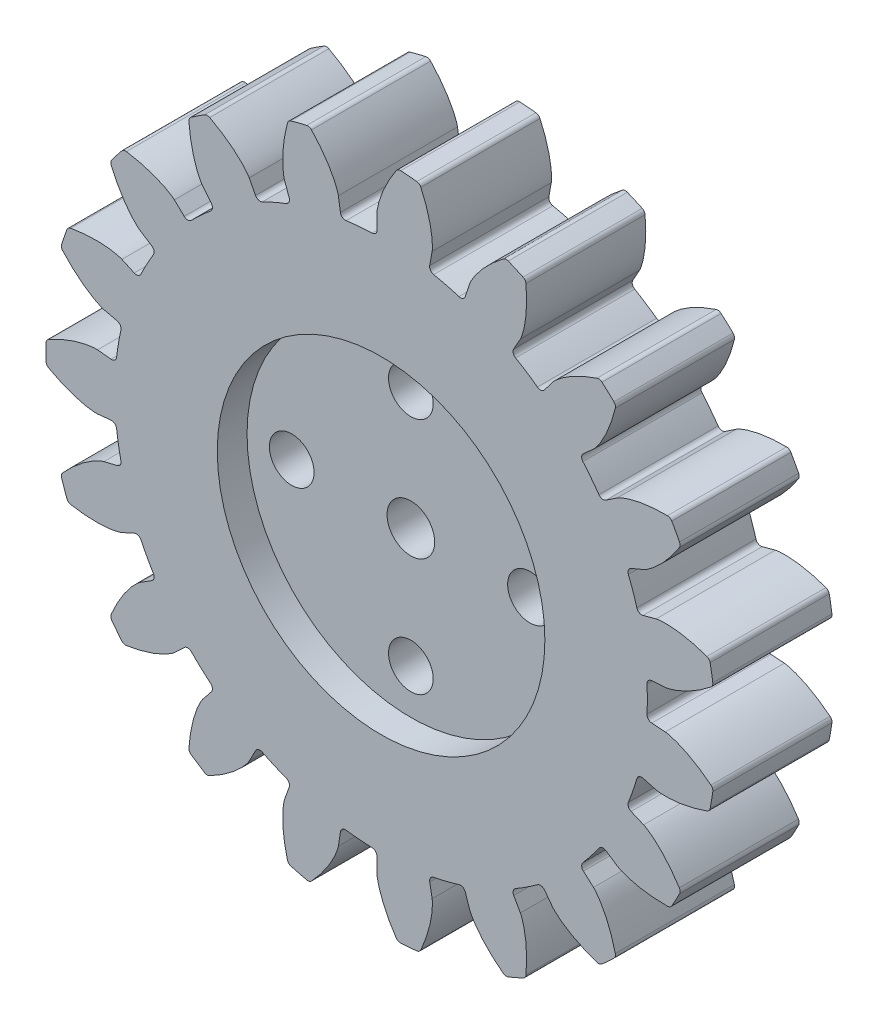
SolidWorks part; units mm, degrees
ref_plane "Front Plane" through (0, 0, 0) normal (0, 0, 1) x (1, 0, 0)
ref_plane "Top Plane" through (0, 0, 0) normal (0, 1, 0) x (1, 0, 0)
ref_plane "Right Plane" through (0, 0, 0) normal (1, 0, 0) x (0, 0, -1)
sketch "Sketch10" plane through (0, 0, 0) normal (0, 0, 1) x (1, 0, 0)
  circle A0 centre (0, 0) radius 22.5
  circle A1 centre (0, 0) radius 1.25
  dimension "D1" = 2.5
  dimension "D2" = 45
extrude "Boss-Extrude5" add sketch "Sketch10" along normal blind 10
sketch "Sketch11" plane through (0, 0, 10) normal (0, 0, 1) x (1, 0, 0)
  line L0 (0, 0) -> (17.88, 0) construction
  line L3 (17.88, 0) -> (22.5005, 0)
  line L4 (0, 0) -> (17.839, 1.2108) construction
  line L5 (19.0859, 1.2954) -> (17.839, 1.2108)
  circle A0 centre (0, 0) radius 17.88 construction
  circle A1 centre (0, 0) radius 19.13 construction
  circle A2 centre (0, 0) radius 20.36 construction
  circle A11 centre (0, 0) radius 22.5005 construction
  arc A12 (22.5005, 0) -> (22.3031, 2.9739) centre (0, 0) ccw
  arc A13 (17.88, 0) -> (17.839, 1.2108) centre (0, 0) ccw
  spline S0 degree 4 poles (19.0859, 1.2954) (19.0913, 1.2959) (19.1065, 1.2973) (19.135, 1.3009) (19.1815, 1.308) (19.2405, 1.3189) (19.3165, 1.335) (19.4057, 1.3566) (19.5032, 1.3831) (19.6089, 1.415) (19.7138, 1.4494) (19.8179, 1.4861) (19.9212, 1.5249) (20.0458, 1.5745) (20.1943, 1.6376) (20.3667, 1.7165) (20.5606, 1.8121) (20.7565, 1.9161) (20.9477, 2.0237) (21.139, 2.1386) (21.3228, 2.254) (21.5117, 2.38) (21.685, 2.4995) (21.8768, 2.6401) (22.0309, 2.7556) (22.2316, 2.915) (22.3493, 3.0113) (22.4861, 3.1265) (22.5464, 3.1789) (22.5835, 3.2111) knots 0 0 0 0 0 0.005377 0.015084 0.028532 0.04661 0.064855 0.092111 0.119476 0.146842 0.174209 0.201575 0.228941 0.256307 0.307035 0.361767 0.4165 0.471232 0.525964 0.580697 0.635429 0.690161 0.744894 0.799626 0.854358 0.909091 0.954545 1 1 1 1 1 construction
  spline S1 degree 4 poles (19.0859, 1.2954) (19.0913, 1.2959) (19.1065, 1.2973) (19.135, 1.3009) (19.1815, 1.308) (19.2405, 1.3189) (19.3165, 1.335) (19.4057, 1.3566) (19.5032, 1.3831) (19.6089, 1.415) (19.7138, 1.4494) (19.8179, 1.4861) (19.9212, 1.5249) (20.0458, 1.5745) (20.1943, 1.6376) (20.3667, 1.7165) (20.5606, 1.8121) (20.7565, 1.9161) (20.9477, 2.0237) (21.139, 2.1386) (21.3228, 2.254) (21.5117, 2.38) (21.685, 2.4995) (21.8768, 2.6401) (22.0309, 2.7556) (22.1881, 2.8805) (22.2643, 2.9421) (22.3031, 2.9739) knots 0 0 0 0 0 0.005377 0.015084 0.028532 0.04661 0.064855 0.092111 0.119476 0.146842 0.174209 0.201575 0.228941 0.256307 0.307035 0.361767 0.4165 0.471232 0.525964 0.580697 0.635429 0.690161 0.744894 0.799626 0.854358 0.909091 0.909091 0.909091 0.909091 0.909091
  dimension "D1" = 40.72
  dimension "D2" = 38.26
  dimension "D3" = 35.76
extrude "Cut-Extrude1" cut sketch "Sketch11" against normal through all
mirror "Mirror1" about plane through (17.88, 0, 0) normal (0, -1, 0) of "Cut-Extrude1"
fillet "Fillet1" radius 0.34 4 edges at (17.839, -1.2108, 5) (22.3026, -2.9735, 5) (22.3026, 2.9735, 5) (17.839, 1.2108, 5)
pattern_circular "CirPattern1" count 19 over 360 about axis through (0, 0, 10) along (0, 0, -1) of "Cut-Extrude1", "Mirror1", "Fillet1" reverse direction yes
sketch "Sketch12" plane through (0, 0, 10) normal (0, 0, 1) x (1, 0, 0)
  circle A2 centre (0, 0) radius 11
  dimension "D1" = 22
extrude "Cut-Extrude2" cut sketch "Sketch12" against normal blind 2
sketch "Sketch13" plane through (0, 0, 8) normal (0, 0, 1) x (1, 0, 0)
  circle A0 centre (0, 0) radius 1.6
  dimension "D1" = 3.2
extrude "Cut-Extrude3" cut sketch "Sketch13" against normal through all
sketch "Sketch14" plane through (0, 0, 8) normal (0, 0, 1) x (1, 0, 0)
  line L0 (0, 0) -> (0, 11) construction
  line L1 (0, 0) -> (-11, 0) construction
  line L2 (0, 0) -> (0, -11) construction
  line L3 (0, 0) -> (11, 0) construction
  circle A0 centre (0, 0) radius 11 construction
  circle A1 centre (0, 0) radius 11 construction
  circle A2 centre (0, 8) radius 1.5
  circle A3 centre (8, 0) radius 1.5
  circle A4 centre (0, -8) radius 1.5
  circle A5 centre (-8, 0) radius 1.5
  dimension "D1" = 3
  dimension "D2" = 8
  dimension "D3" = 8
  dimension "D4" = 8
  dimension "D5" = 8
extrude "Cut-Extrude4" cut sketch "Sketch14" against normal blind 6
sketch "Croquis1" plane through (0, 0, 0) normal (0, 0, -1) x (-1, 0, 0)
  line L1 (-29.3017, 25.5972) -> (30.0749, 25.5972)
  line L2 (-29.3017, 25.5972) -> (-29.3017, -25.9289)
  line L3 (-29.3017, -25.9289) -> (30.0749, -25.9289)
  line L4 (30.0749, 25.5972) -> (30.0749, -25.9289)
extrude "Cortar-Extruir1" cut sketch "Croquis1" against normal blind 2
equation "\"P\"= 0.466657"
equation "\"z\"= 19"
equation "\"α\"= 20"
equation "\"s\"= 5"
equation "\"D_b\"= 2.5"
equation "\"c\"= 0.157 / \"P\""
equation "\"D_p\"= \"z\" / \"P\""
equation "\"D_base\"= \"D_p\" * cos ( \"α\" )"
equation "\"h_a\"= 1 / \"P\""
equation "\"h_d\"= 1 / \"P\" + \"c\""
equation "\"P_c\"= pi / \"P\""
equation "\"D_a\"= \"D_p\" + ( 2 * \"h_a\" )"
equation "\"D_d\"= \"D_p\" - ( 2 * \"h_d\" )"
equation "\"φ\"= 360 / \"z\""
equation "\"α_inv\"= ( ( \"D_p\" ^ 2 - \"D_base\" ^ 2 ) ^ 0.5 / \"D_base\" ) * 180 / pi - \"α\""
equation "\"β_inv\"= ( \"φ\" / 4 ) - \"α_inv\""
equation "\"ζ\"= ( ( \"D_a\" / 2 ) ^ 2 - ( \"D_base\" / 2 ) ^ 2 ) ^ 0.5 * 2 / \"D_base\""
